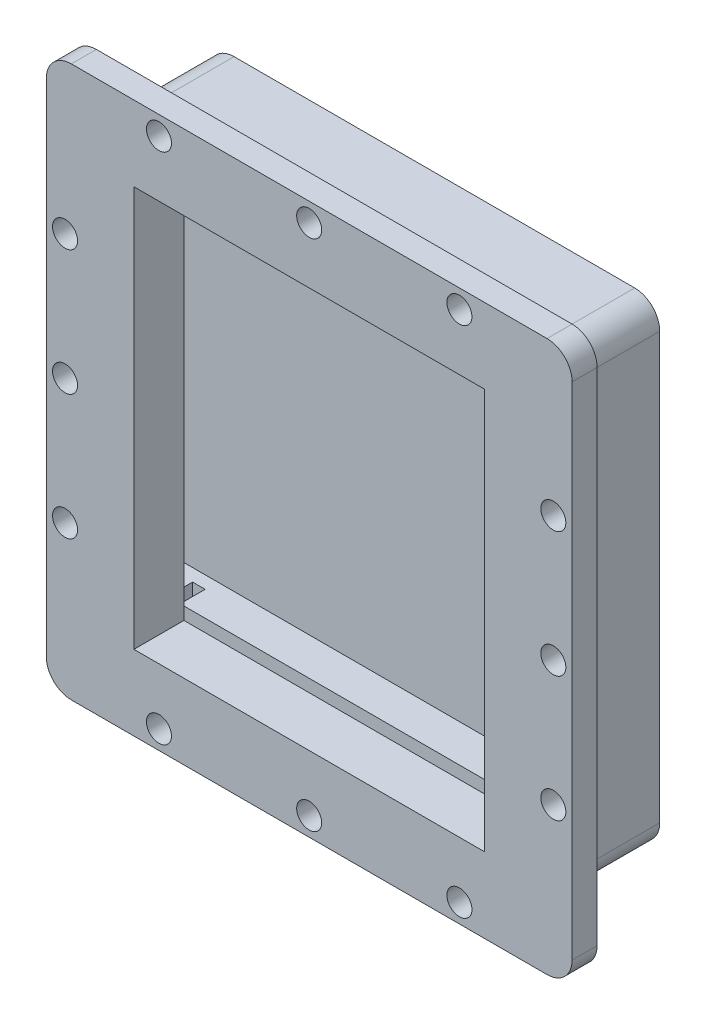
SolidWorks part; units mm, degrees
ref_plane "前视基准面" through (0, 0, 0) normal (0, 0, 1) x (1, 0, 0)
ref_plane "上视基准面" through (0, 0, 0) normal (0, 1, 0) x (1, 0, 0)
ref_plane "右视基准面" through (0, 0, 0) normal (1, 0, 0) x (0, 0, -1)
sketch "草图1" plane through (0, 0, 0) normal (0, 0, 1) x (1, 0, 0)
  line L1 (-80, -95) -> (80, -95)
  line L2 (-90, -85) -> (-90, 85)
  line L3 (-80, 95) -> (80, 95)
  line L4 (90, -85) -> (90, 85)
  line L5 (-90, -95) -> (90, 95) construction
  line L6 (-90, 95) -> (90, -95) construction
  arc A0 (80, -95) -> (90, -85) centre (80, -85) ccw
  arc A1 (-80, -95) -> (-90, -85) centre (-80, -85) cw
  arc A2 (-90, 85) -> (-80, 95) centre (-80, 85) cw
  arc A3 (80, 95) -> (90, 85) centre (80, 85) cw
  point P0 (0, 0)
  dimension "D3" = 10
  dimension "D1" = 190
  dimension "D2" = 180
extrude "凸台-拉伸1" add sketch "草图1" along normal blind 40
sketch "草图7" plane through (0, 0, 40) normal (0, 0, 1) x (1, 0, 0)
  line L0 (0, 0) -> (0, 102.5) construction
  line L1 (-95, -110) -> (95, -110)
  line L2 (-105, -100) -> (-105, 100)
  line L3 (-95, 110) -> (95, 110)
  line L4 (105, -100) -> (105, 100)
  line L5 (-105, -110) -> (105, 110) construction
  line L6 (-105, 110) -> (105, -110) construction
  line L11 (-74.6232, -78.5508) -> (74.6232, 78.5508) construction
  line L12 (-75.1674, 78.7468) -> (74.4532, -77.9985) construction
  line L13 (0, 0) -> (97.5, 0) construction
  line L15 (-97.5, -102.5) -> (97.5, -102.5) construction
  line L16 (-97.5, -102.5) -> (-97.5, 102.5) construction
  line L17 (-97.5, 102.5) -> (97.5, 102.5) construction
  line L18 (97.5, -102.5) -> (97.5, 102.5) construction
  line L19 (-97.5, -102.5) -> (97.5, 102.5) construction
  line L20 (-97.5, 102.5) -> (97.5, -102.5) construction
  arc A0 (95, -110) -> (105, -100) centre (95, -100) ccw
  arc A1 (-95, -110) -> (-105, -100) centre (-95, -100) cw
  arc A2 (95, 110) -> (105, 100) centre (95, 100) cw
  arc A3 (-105, 100) -> (-95, 110) centre (-95, 100) cw
  circle A4 centre (0, 102.5) radius 5
  circle A5 centre (-60, 102.5) radius 5
  circle A6 centre (-97.5, 0) radius 5
  circle A7 centre (-97.5, 50) radius 5
  circle A8 centre (97.5, 0) radius 5
  circle A9 centre (97.5, 50) radius 5
  circle A10 centre (60, 102.5) radius 5
  circle A11 centre (-97.5, -50) radius 5
  circle A12 centre (97.5, -50) radius 5
  circle A13 centre (60, -102.5) radius 5
  circle A14 centre (0, -102.5) radius 5
  circle A15 centre (-60, -102.5) radius 5
  point P0 (0, 0)
  point P18 (0, 0)
  dimension "D3" = 10
  dimension "D6" = 10
  dimension "D7" = 10
  dimension "D8" = 60
  dimension "D9" = 10
  dimension "D10" = 10
  dimension "D11" = 50
  dimension "D1" = 220
  dimension "D2" = 210
  dimension "D4" = 195
  dimension "D5" = 205
extrude "凸台-拉伸2" add sketch "草图7" along normal blind 10
sketch "草图8" plane through (0, 0, 50) normal (0, 0, 1) x (1, 0, 0)
  line L1 (-70, -80) -> (70, -80)
  line L2 (-70, -80) -> (-70, 80)
  line L3 (-70, 80) -> (70, 80)
  line L4 (70, -80) -> (70, 80)
  line L5 (-70, -80) -> (70, 80) construction
  line L6 (-70, 80) -> (70, -80) construction
  point P0 (0, 0)
  dimension "D1" = 160
  dimension "D2" = 140
extrude "切除-拉伸4" cut sketch "草图8" against normal blind 40
sketch "草图5" plane through (-90, 0, 0) normal (-1, 0, 0) x (0, 0, 1)
  line L0 (0, 0) -> (30, 0) construction
  line L1 (10, -80) -> (10, 80)
  line L2 (30.0153, 85) -> (25.0153, 85)
  line L3 (10, 80) -> (25.0153, 80)
  line L4 (30, 80) -> (30, -80)
  line L5 (10, -80) -> (25.0153, -80)
  line L6 (0, 85) -> (0, -85) construction
  line L7 (30.0153, 80) -> (30.0153, 85)
  line L8 (30.0153, 85) -> (25.0153, 85)
  line L9 (40, 85) -> (0, 85) construction
  line L10 (25.0153, 85) -> (25.0153, 80)
  line L11 (30.0153, 80) -> (30, 80)
  line L12 (25.0153, -85) -> (25.0153, -80)
  line L13 (30.0153, -85) -> (25.0153, -85)
  line L14 (30.0153, -80) -> (30.0153, -85)
  line L15 (30.0153, -85) -> (25.0153, -85)
  line L16 (30.0153, -80) -> (30, -80)
  line M7 (0, -85) -> (40, -85)
  line M9 (40, 85) -> (0, 85)
  dimension "D1" = 160
  dimension "D2" = 20
  dimension "D3" = 10
  dimension "D5" = 5
  dimension "D6" = 5
extrude "切除-拉伸5" cut sketch "草图5" against normal blind 160 contours L1 L0 L4 L11 L7 L10 L3 M9 | L0 L1 L5 L12 L14 L16 L4 M7 region at (-90, 40.6538, 20.1156) region at (-90, -40.6538, 20.1156)
sketch "草图10" plane through (0, 0, 25.0153) normal (0, 0, 1) x (1, 0, 0)
  line L0 (70, 80) -> (-90, 80) construction
  line L1 (-81.5414, 80) -> (-81.5414, 85)
  line L2 (-81.5414, 85) -> (-76.5414, 85)
  line L3 (-76.5414, 85) -> (-76.5414, 80)
  line L4 (-76.5414, 80) -> (-81.5414, 80)
  line L5 (0, 0) -> (-23.276, 0) construction
  line L6 (0, 0) -> (0, 24.2919) construction
  line L7 (55, 80) -> (55, 85)
  line L8 (55, 85) -> (50, 85)
  line L9 (50, 85) -> (50, 80)
  line L10 (70, -80) -> (70, 80) construction
  line L11 (55, 80) -> (50, 80)
  line L12 (55, -80) -> (50, -80)
  line L13 (50, -85) -> (50, -80)
  line L14 (55, -85) -> (50, -85)
  line L15 (55, -80) -> (55, -85)
  line L16 (-76.5414, -80) -> (-81.5414, -80)
  line L17 (-76.5414, -85) -> (-76.5414, -80)
  line L18 (-81.5414, -85) -> (-76.5414, -85)
  line L19 (-81.5414, -80) -> (-81.5414, -85)
  dimension "D1" = 160
  dimension "D2" = 5
  dimension "D3" = 5
  dimension "D4" = 5
  dimension "D5" = 5
  dimension "D6" = 15
extrude "切除-拉伸6" cut sketch "草图10" against normal blind 10
